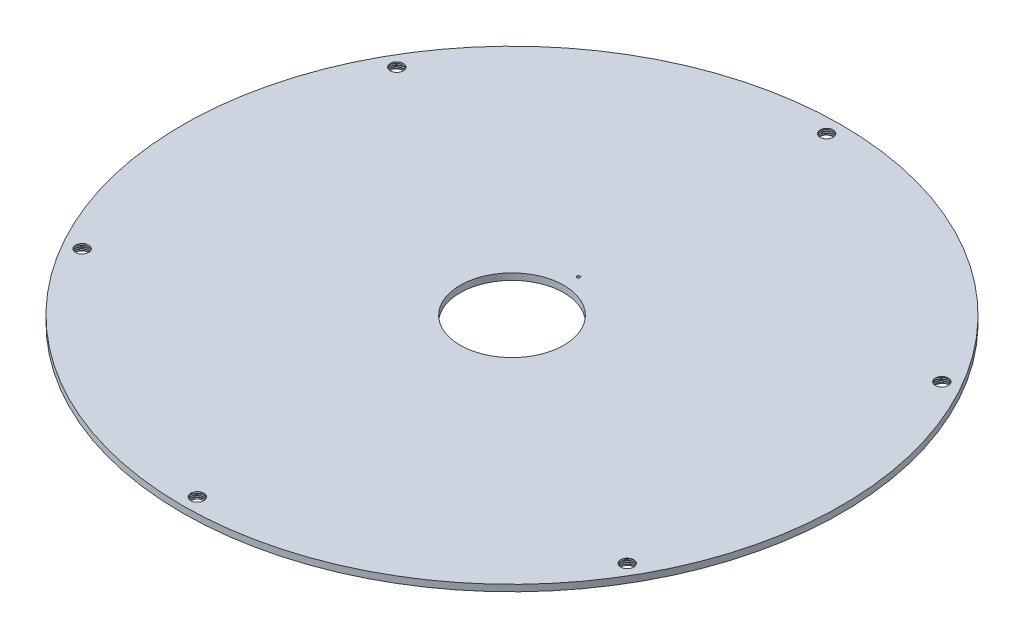
SolidWorks part; units mm, degrees
material "1060 Alloy"
ref_plane "Front Plane" through (0, 0, 0) normal (0, 0, 1) x (1, 0, 0)
ref_plane "Top Plane" through (0, 0, 0) normal (0, 1, 0) x (1, 0, 0)
ref_plane "Right Plane" through (0, 0, 0) normal (1, 0, 0) x (0, 0, -1)
sketch "Sketch1" plane through (0, 0, 0) normal (0, 1, 0) x (1, 0, 0)
  circle A0 centre (0, 0) radius 50.8
  circle A1 centre (0, 0) radius 8
  circle A2 centre (0, 48.5) radius 1
  circle A3 centre (42.0022, 24.25) radius 1
  circle A4 centre (42.0022, -24.25) radius 1
  circle A5 centre (0, -48.5) radius 1
  circle A6 centre (-42.0022, -24.25) radius 1
  circle A7 centre (-42.0022, 24.25) radius 1
  point P18 (0, 0)
  dimension "D1" = 101.6
  dimension "D2" = 16
  dimension "D3" = 2
  dimension "D4" = 48.5
  dimension "D5" = 6
extrude "Boss-Extrude1" add sketch "Sketch1" along normal blind 1
thread "Thread1" pitch 0.25 profile "Thread Profile1" start angle 0, offset 0, length 10, pitch 0.25, diameter 2
ref_plane "Plane1" through (-1, 1, 48.5) normal (0, 0, 1) x (-1, 0, 0)
sketch "Thread Profile1" plane through (-1, 1, 48.5) normal (0, 0, 1) x (-1, 0, 0)
  line L0 (0, 0) -> (0, 0.25) construction
  line L1 (0, 0) -> (0.1353, 0.0781)
  line L2 (0.1353, 0.0781) -> (0.1353, 0.1094)
  line L3 (0.1353, 0.1094) -> (0, 0.1875)
  line L4 (0.1353, 0.0937) -> (0, 0.0937) construction
  line L11 (0, 0) -> (0, 0.1875)
  point P2 (0, 0)
  dimension "Pitch" = 0.25
  dimension "Profile_Angle" = 60
  dimension "Profile_Land" = 0.0312
  dimension "Profile_Height" = 0.1353
pattern_circular "CirPattern1" count 6 over 360 about axis through (0, 0, 0) along (0, 1, 0) of "Thread1"
sketch "Sketch2" plane through (0, 1, 0) normal (0, 1, 0) x (1, 0, 0)
  circle A0 centre (0, 10.25) radius 0.25
  dimension "D1" = 0.5
  dimension "D2" = 10.25
extrude "Cut-Extrude1" cut sketch "Sketch2" against normal through all both and the other way through all
